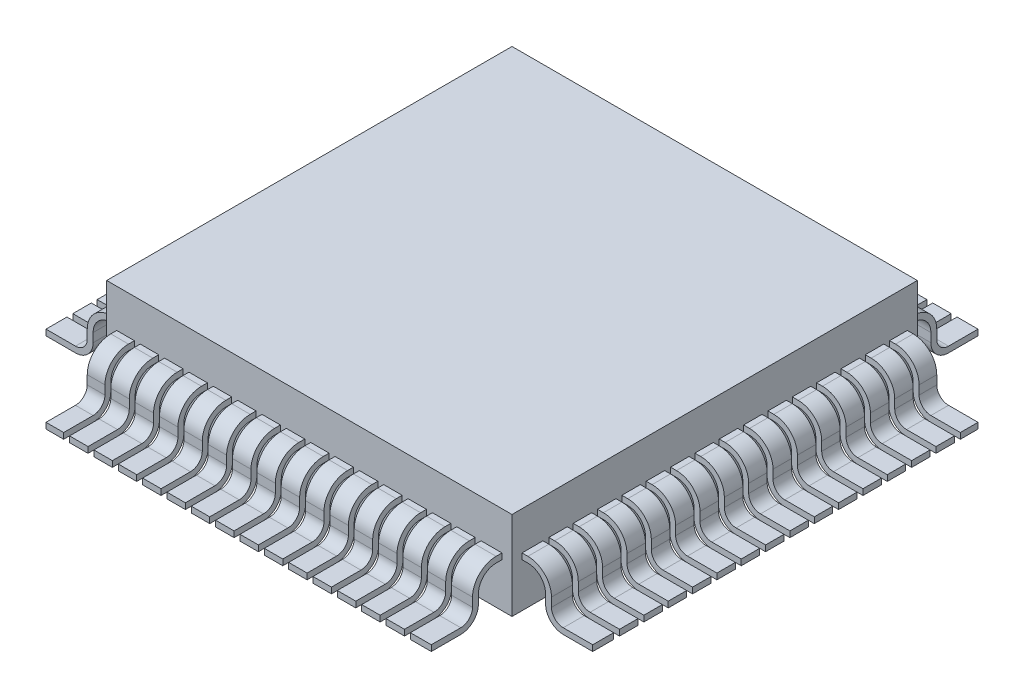
SolidWorks part; units mm, degrees
material "45"
ref_plane "前视基准面" through (0, 0, 0) normal (0, 0, 1) x (1, 0, 0)
ref_plane "上视基准面" through (0, 0, 0) normal (0, 1, 0) x (1, 0, 0)
ref_plane "右视基准面" through (0, 0, 0) normal (1, 0, 0) x (0, 0, -1)
sketch "草图1" plane through (0, 0, 0) normal (0, 1, 0) x (1, 0, 0)
  line L1 (-3.44, 3.44) -> (3.44, 3.44)
  line L2 (-3.44, 3.44) -> (-3.44, -3.44)
  line L3 (-3.44, -3.44) -> (3.44, -3.44)
  line L4 (3.44, 3.44) -> (3.44, -3.44)
  line L5 (-3.44, 3.44) -> (3.44, -3.44) construction
  line L6 (-3.44, -3.44) -> (3.44, 3.44) construction
  point P0 (0, 0)
  dimension "D1" = 6.88
  dimension "D2" = 6.88
extrude "凸台-拉伸1" add sketch "草图1" along normal blind 1.5
sketch "草图2" plane through (0, 0, 3.44) normal (0, 0, 1) x (1, 0, 0)
  line L0 (-3.44, 0.75) -> (-3.54, 0.75)
  line L1 (-3.44, 1.5) -> (-3.44, 0) construction
  line L2 (-3.84, 0.45) -> (-3.84, 0.3)
  line L3 (-4.14, 0) -> (-4.64, 0)
  arc A0 (-3.84, 0.3) -> (-4.14, 0) centre (-4.14, 0.3) cw
  arc A1 (-3.54, 0.75) -> (-3.84, 0.45) centre (-3.54, 0.45) ccw
  point P11 (-3.84, 0.75)
  dimension "D3" = 0.3
  dimension "D1" = 1.2
  dimension "D2" = 0.4
extrude "拉伸-薄壁1" add sketch "草图2" against normal up to surface (6.88 mm away) thin up to face at (0, 0.75, -3.44) thin type one direction wall 0.1
sketch "草图3" plane through (0, 1.5, 0) normal (0, 1, 0) x (1, 0, 0)
  line L0 (-3.44, 3.44) -> (-3.44, -3.44) construction
  line L1 (-4.64, 3.44) -> (-3.44, 3.44)
  line L2 (-4.64, 3.44) -> (-4.64, 3.27)
  line L3 (-4.64, 3.27) -> (-3.44, 3.27)
  line L4 (-3.44, 3.44) -> (-3.44, 3.27)
  line L5 (-3.44, 3.44) -> (-3.44, -3.44) construction
  line L6 (-4.64, -3.44) -> (-3.44, -3.44)
  line L7 (-4.64, -3.44) -> (-4.64, -3.27)
  line L8 (-4.64, -3.27) -> (-3.44, -3.27)
  line L9 (-3.44, -3.44) -> (-3.44, -3.27)
  dimension "D1" = 6.54
extrude "切除-拉伸1" cut sketch "草图3" against normal blind 1.5
sketch "草图4" plane through (0, 1.5, 0) normal (0, 1, 0) x (1, 0, 0)
  line L0 (-4.64, 3.27) -> (-4.64, -3.27) construction
  line L1 (-4.64, 2.97) -> (-3.44, 2.97)
  line L2 (-4.64, 2.97) -> (-4.64, 2.87)
  line L3 (-4.64, 2.87) -> (-3.44, 2.87)
  line L4 (-3.44, 2.97) -> (-3.44, 2.87)
  line L5 (-3.44, 3.44) -> (-3.44, -3.44) construction
  line L6 (-4.64, 3.27) -> (-4.14, 3.27) construction
  dimension "D1" = 0.3
  dimension "D2" = 0.1
extrude "切除-拉伸2" cut sketch "草图4" against normal blind 1.5
pattern_linear "阵列(线性)1" count 15 spacing 0.4132 along (0, 0, 1) of "切除-拉伸2"
sketch "草图5" plane through (0, 0, 0) normal (0, -1, 0) x (1, 0, 0)
  circle A0 centre (0, 0) radius 0.1315
extrude "切除-拉伸3" cut sketch "草图5" against normal blind 1
mirror "镜向2" about plane through (0, 0, 0) normal (1, 0, 0) of "阵列(线性)1", "切除-拉伸2", "切除-拉伸1", "拉伸-薄壁1"
sketch "草图6" plane through (-3.44, 0, 0) normal (-1, 0, 0) x (0, 0, 1)
  line L0 (-3.44, 0.75) -> (-3.54, 0.75)
  line L1 (-3.44, 1.5) -> (-3.44, 0) construction
  line L2 (-3.84, 0.45) -> (-3.84, 0.3)
  line L3 (-4.14, 0) -> (-4.64, 0)
  arc A0 (-3.84, 0.3) -> (-4.14, 0) centre (-4.14, 0.3) cw
  arc A1 (-3.54, 0.75) -> (-3.84, 0.45) centre (-3.54, 0.45) ccw
  point P11 (-3.84, 0.75)
  dimension "D3" = 0.3
  dimension "D1" = 1.2
  dimension "D2" = 0.4
extrude "拉伸-薄壁2" add sketch "草图6" against normal up to surface (6.88 mm away) thin up to face at (3.44, 0.8, 3.0036) thin type one direction wall 0.1
sketch "草图7" plane through (0, 1.5, 0) normal (0, 1, 0) x (1, 0, 0)
  line L0 (3.44, 3.44) -> (-3.44, 3.44) construction
  line L1 (-3.44, 4.64) -> (-3.27, 4.64)
  line L2 (-3.44, 4.64) -> (-3.44, 3.44)
  line L3 (-3.44, 3.44) -> (-3.27, 3.44)
  line L4 (-3.27, 4.64) -> (-3.27, 3.44)
  line L6 (3.44, 4.64) -> (3.27, 4.64)
  line L7 (3.44, 4.64) -> (3.44, 3.44)
  line L8 (3.44, 3.44) -> (3.27, 3.44)
  line L9 (3.27, 4.64) -> (3.27, 3.44)
  dimension "D1" = 0.17
  dimension "D2" = 0.17
extrude "切除-拉伸4" cut sketch "草图7" against normal up to next
sketch "草图8" plane through (0, 1.5, 0) normal (0, 1, 0) x (1, 0, 0)
  line L0 (3.27, 3.44) -> (-3.27, 3.44) construction
  line L1 (-2.97, 3.44) -> (-2.87, 3.44)
  line L2 (-2.97, 3.44) -> (-2.97, 4.64)
  line L3 (-2.97, 4.64) -> (-2.87, 4.64)
  line L4 (-2.87, 3.44) -> (-2.87, 4.64)
  line L5 (3.27, 4.64) -> (-3.27, 4.64) construction
  line L6 (-3.27, 4.64) -> (-3.27, 4.14) construction
  dimension "D1" = 0.3
  dimension "D2" = 0.1
extrude "切除-拉伸5" cut sketch "草图8" against normal up to next
pattern_linear "阵列(线性)2" count 15 spacing 0.4132 along (1, 0, 0) of "切除-拉伸5"
mirror "镜向3" about plane through (0, 0, 0) normal (0, 0, 1) of "阵列(线性)2", "切除-拉伸5", "切除-拉伸4", "拉伸-薄壁2"
